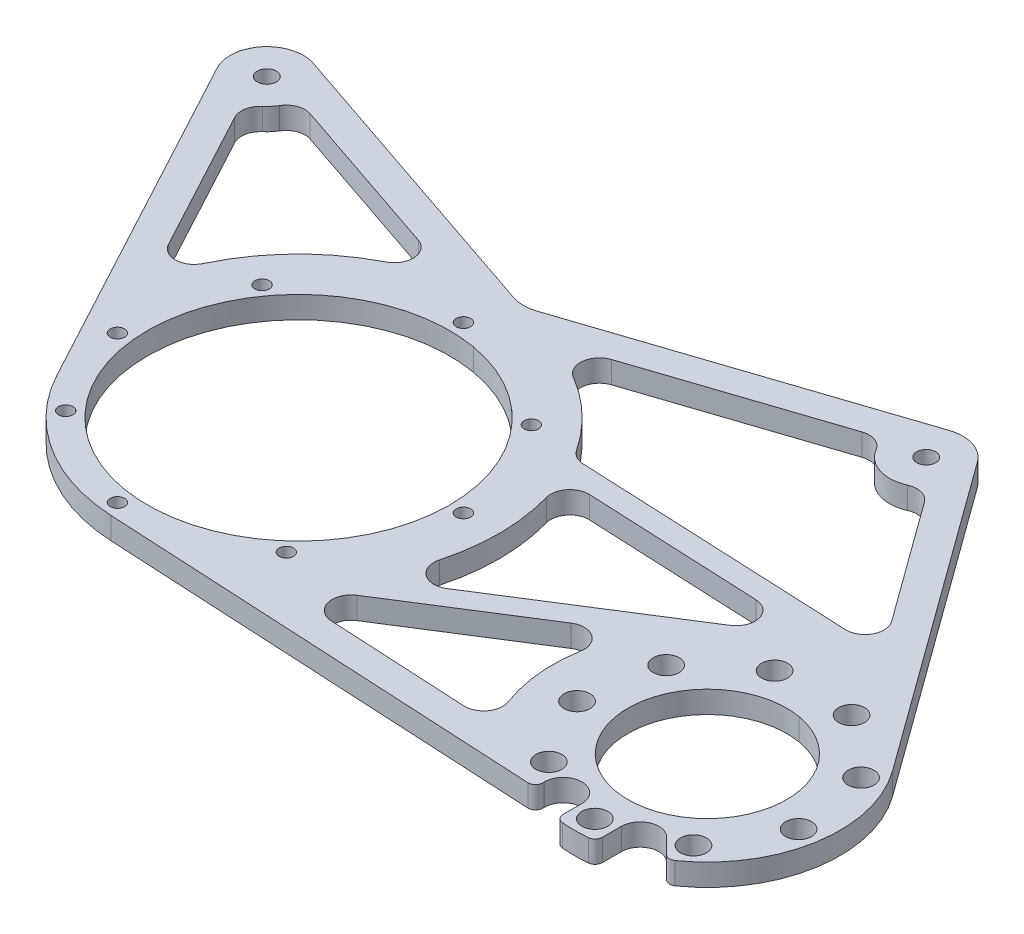
SolidWorks part; units mm, degrees
material "6061-T6 (SS)"
ref_plane "X-Y Datum" through (0, 0, 0) normal (0, 0, 1) x (1, 0, 0)
ref_plane "X-Z Datum" through (0, 0, 0) normal (0, 1, 0) x (1, 0, 0)
ref_plane "Y-Z Datum" through (0, 0, 0) normal (1, 0, 0) x (0, 0, -1)
sketch "Sketch2" plane through (0, 31.3819, 0) normal (0, 1, 0) x (1, 0, 0)
  line L0 (-693.7583, -176.702) -> (-693.7583, -183.2747) construction
  line L1 (-680.0808, -183.2747) -> (-680.0808, -176.702) construction
  line L2 (-668.9846, -172.1058) -> (-663.7197, -177.3707) construction
  line L3 (-693.7583, -176.702) -> (-693.7583, -183.2747)
  line L4 (-680.0808, -183.2747) -> (-680.0808, -176.702)
  line L5 (-668.9846, -172.1058) -> (-663.7197, -177.3707)
  line L6 (-966.641, -0.354) -> (-738.041, -0.354)
  line L7 (-727.7656, -5.5904) -> (-649.7224, -113.0358)
  line L9 (-977.8288, -19.0644) -> (-913.2312, -139.3061)
  line L10 (-706.7583, -177.279) -> (-706.7583, -176.702) construction
  line L11 (-706.7583, -177.279) -> (-706.7583, -176.702)
  line L12 (-861.9259, -171.8334) -> (-709.2983, -179.819)
  line L13 (-858.691, -110.0055) -> (-686.9195, -140.054) construction
  arc A0 (-710.607, -179.4559) -> (-706.7583, -177.279) centre (-709.2983, -177.279) ccw construction
  arc A1 (-693.7583, -176.702) -> (-706.7583, -176.702) centre (-700.2583, -176.702) ccw construction
  arc A2 (-693.7583, -183.2747) -> (-691.4697, -185.8023) centre (-691.2183, -183.2747) ccw construction
  arc A3 (-691.4697, -185.8023) -> (-682.3694, -185.8023) centre (-686.9195, -140.054) ccw construction
  arc A4 (-682.3694, -185.8023) -> (-680.0808, -183.2747) centre (-682.6208, -183.2747) ccw construction
  arc A5 (-668.9846, -172.1058) -> (-680.0808, -176.702) centre (-673.5808, -176.702) ccw construction
  arc A6 (-663.7197, -177.3707) -> (-660.4619, -177.6519) centre (-661.9236, -175.5746) ccw construction
  arc A7 (-660.4619, -177.6519) -> (-710.607, -179.4559) centre (-686.9195, -140.054) ccw construction
  circle A8 centre (-858.691, -110.0055) radius 52.3875 construction
  circle A9 centre (-858.691, -110.0055) radius 61.9125 construction
  circle A10 centre (-738.041, -13.054) radius 12.7 construction
  circle A11 centre (-966.641, -13.054) radius 12.7 construction
  arc A12 (-710.607, -179.4559) -> (-706.7583, -177.279) centre (-709.2983, -177.279) ccw
  arc A13 (-693.7583, -176.702) -> (-706.7583, -176.702) centre (-700.2583, -176.702) ccw
  arc A14 (-693.7583, -183.2747) -> (-691.4697, -185.8023) centre (-691.2183, -183.2747) ccw
  arc A15 (-691.4697, -185.8023) -> (-682.3694, -185.8023) centre (-686.9195, -140.054) ccw
  arc A16 (-682.3694, -185.8023) -> (-680.0808, -183.2747) centre (-682.6208, -183.2747) ccw
  arc A17 (-668.9846, -172.1058) -> (-680.0808, -176.702) centre (-673.5808, -176.702) ccw
  arc A18 (-663.7197, -177.3707) -> (-660.4619, -177.6519) centre (-661.9236, -175.5746) ccw
  arc A19 (-660.4619, -177.6519) -> (-710.607, -179.4559) centre (-686.9195, -140.054) ccw
  circle A20 centre (-858.691, -110.0055) radius 52.3875
  circle A21 centre (-858.691, -110.0055) radius 61.9125
  circle A22 centre (-738.041, -13.054) radius 12.7
  circle A23 centre (-966.641, -13.054) radius 12.7
  circle A24 centre (-901.1618, -148.2463) radius 2.5 construction
  circle A25 centre (-915.528, -115.9793) radius 2.5 construction
  circle A26 centre (-904.9264, -76.4135) radius 2.5 construction
  circle A27 centre (-858.691, -52.8555) radius 2.5 construction
  circle A28 centre (-816.2203, -71.7646) radius 2.5 construction
  circle A29 centre (-801.541, -110.0055) radius 2.5 construction
  circle A30 centre (-820.4502, -152.4762) radius 2.5 construction
  circle A31 centre (-864.6648, -166.8424) radius 2.5 construction
  circle A32 centre (-901.1618, -148.2463) radius 2.5
  circle A33 centre (-915.528, -115.9793) radius 2.5
  circle A34 centre (-904.9264, -76.4135) radius 2.5
  circle A35 centre (-858.691, -52.8555) radius 2.5
  circle A36 centre (-816.2203, -71.7646) radius 2.5
  circle A37 centre (-801.541, -110.0055) radius 2.5
  circle A38 centre (-820.4502, -152.4762) radius 2.5
  circle A39 centre (-864.6648, -166.8424) radius 2.5
  circle A40 centre (-686.9195, -140.054) radius 27.4955 construction
  circle A41 centre (-686.9195, -140.054) radius 27.4955
  circle A42 centre (-711.9883, -169.9297) radius 4.5 construction
  circle A43 centre (-725.3271, -146.8263) radius 4.5 construction
  circle A44 centre (-720.6945, -120.554) radius 4.5 construction
  circle A45 centre (-700.2583, -103.406) radius 4.5 construction
  circle A46 centre (-673.5808, -103.406) radius 4.5 construction
  circle A47 centre (-653.1446, -120.554) radius 4.5 construction
  circle A48 centre (-648.512, -146.8263) radius 4.5 construction
  circle A49 centre (-661.8508, -169.9297) radius 4.5 construction
  circle A50 centre (-686.9195, -179.054) radius 4.5 construction
  circle A51 centre (-711.9883, -169.9297) radius 4.5
  circle A52 centre (-725.3271, -146.8263) radius 4.5
  circle A53 centre (-720.6945, -120.554) radius 4.5
  circle A54 centre (-700.2583, -103.406) radius 4.5
  circle A55 centre (-673.5808, -103.406) radius 4.5
  circle A56 centre (-653.1446, -120.554) radius 4.5
  circle A57 centre (-648.512, -146.8263) radius 4.5
  circle A58 centre (-661.8508, -169.9297) radius 4.5
  circle A59 centre (-686.9195, -179.054) radius 4.5
  circle A60 centre (-966.641, -13.054) radius 3.3
  circle A61 centre (-738.041, -13.054) radius 3.3
  dimension "D1" = 6.6
  dimension "D2" = 6.6
extrude "Boss-Extrude1" add sketch "Sketch2" along normal blind 7.62 contours A21 A39 A38 A37 A36 A35 A34 A33 A32 A20 | A23 L9 A21 A19 L7 A22 L6 | A18 A19 A12 L11 A13 L3 A14 A15 A16 L4 A17 L5 A59 A58 A57 A56 A55 A54 A53 A52 A51 A41 | A23 A60 | A22 A61 | L13 A21 L12 A12 A19 region at (-700.2583, 31.3819, 168.9016) region at (-773.051, 31.3819, 154.3682) region at (-890.9045, 31.3819, 160.8157) region at (-815.2898, 31.3819, 52.4464) region at (-977.2328, 31.3819, 6.7207) region at (-726.304, 31.3819, 9.2412)
sketch "Sketch3" plane through (0, 31.3819, 0) normal (0, -1, 0) x (1, 0, 0)
  line L5 (-861.9259, 171.8334) -> (-709.2983, 179.819) construction
  line L6 (-977.8288, 19.0644) -> (-913.2312, 139.3061) construction
  line L7 (-727.7656, 5.5904) -> (-649.7224, 113.0358) construction
  line L16 (-966.641, 0.354) -> (-738.041, 0.354) construction
  line L19 (-663.7197, 177.3707) -> (-668.9846, 172.1058)
  line L20 (-680.0808, 176.702) -> (-680.0808, 183.2747)
  line L21 (-693.7583, 183.2747) -> (-693.7583, 176.702)
  line L22 (-706.7583, 176.702) -> (-706.7583, 177.279)
  line L23 (-663.7197, 177.3707) -> (-668.9846, 172.1058)
  line L24 (-680.0808, 176.702) -> (-680.0808, 183.2747)
  line L25 (-693.7583, 183.2747) -> (-693.7583, 176.702)
  line L26 (-706.7583, 176.702) -> (-706.7583, 177.279)
  line L28 (-861.9259, 171.8334) -> (-709.2983, 179.819)
  line L29 (-977.8288, 19.0644) -> (-913.2312, 139.3061)
  line L30 (-727.7656, 5.5904) -> (-649.7224, 113.0358)
  line L31 (-966.641, 0.354) -> (-738.041, 0.354)
  line L32 (-962.5646, 1.026) -> (-853.4371, 38.0109)
  line L33 (-853.4371, 38.0109) -> (-742.0453, 1.0018)
  circle A3 centre (-966.641, 13.054) radius 12.7
  circle A5 centre (-966.641, 13.054) radius 12.7
  circle A7 centre (-738.041, 13.054) radius 12.7
  circle A9 centre (-738.041, 13.054) radius 12.7
  circle A11 centre (-858.691, 110.0055) radius 61.9125
  circle A13 centre (-858.691, 110.0055) radius 61.9125
  circle A15 centre (-858.691, 110.0055) radius 52.3875
  circle A17 centre (-858.691, 110.0055) radius 52.3875
  circle A19 centre (-686.9195, 140.054) radius 27.4955
  circle A21 centre (-686.9195, 140.054) radius 27.4955
  circle A23 centre (-864.6648, 166.8424) radius 2.5
  circle A25 centre (-864.6648, 166.8424) radius 2.5
  circle A27 centre (-820.4502, 152.4762) radius 2.5
  circle A29 centre (-820.4502, 152.4762) radius 2.5
  circle A31 centre (-801.541, 110.0055) radius 2.5
  circle A33 centre (-801.541, 110.0055) radius 2.5
  circle A35 centre (-816.2203, 71.7646) radius 2.5
  circle A37 centre (-816.2203, 71.7646) radius 2.5
  circle A39 centre (-858.691, 52.8555) radius 2.5
  circle A41 centre (-858.691, 52.8555) radius 2.5
  circle A43 centre (-904.9264, 76.4135) radius 2.5
  circle A46 centre (-904.9264, 76.4135) radius 2.5
  circle A47 centre (-915.528, 115.9793) radius 2.5
  circle A48 centre (-915.528, 115.9793) radius 2.5
  circle A49 centre (-901.1618, 148.2463) radius 2.5
  circle A50 centre (-901.1618, 148.2463) radius 2.5
  circle A51 centre (-720.6945, 120.554) radius 4.5
  circle A52 centre (-720.6945, 120.554) radius 4.5
  circle A68 centre (-725.3271, 146.8263) radius 4.5
  circle A69 centre (-725.3271, 146.8263) radius 4.5
  circle A70 centre (-711.9883, 169.9297) radius 4.5
  circle A71 centre (-711.9883, 169.9297) radius 4.5
  circle A72 centre (-738.041, 13.054) radius 3.3
  circle A73 centre (-738.041, 13.054) radius 3.3
  circle A74 centre (-966.641, 13.054) radius 3.3
  circle A75 centre (-966.641, 13.054) radius 3.3
  circle A76 centre (-686.9195, 179.054) radius 4.5
  circle A77 centre (-686.9195, 179.054) radius 4.5
  circle A78 centre (-661.8508, 169.9297) radius 4.5
  circle A79 centre (-661.8508, 169.9297) radius 4.5
  circle A80 centre (-648.512, 146.8263) radius 4.5
  circle A81 centre (-648.512, 146.8263) radius 4.5
  circle A82 centre (-653.1446, 120.554) radius 4.5
  circle A83 centre (-653.1446, 120.554) radius 4.5
  circle A84 centre (-673.5808, 103.406) radius 4.5
  circle A85 centre (-673.5808, 103.406) radius 4.5
  circle A86 centre (-700.2583, 103.406) radius 4.5
  circle A87 centre (-700.2583, 103.406) radius 4.5
  arc A95 (-710.607, 179.4559) -> (-660.4619, 177.6519) centre (-686.9195, 140.054) ccw
  arc A96 (-660.4619, 177.6519) -> (-663.7197, 177.3707) centre (-661.9236, 175.5746) ccw
  arc A97 (-680.0808, 176.702) -> (-668.9846, 172.1058) centre (-673.5808, 176.702) ccw
  arc A98 (-680.0808, 183.2747) -> (-682.3694, 185.8023) centre (-682.6208, 183.2747) ccw
  arc A99 (-682.3694, 185.8023) -> (-691.4697, 185.8023) centre (-686.9195, 140.054) ccw
  arc A100 (-691.4697, 185.8023) -> (-693.7583, 183.2747) centre (-691.2183, 183.2747) ccw
  arc A101 (-706.7583, 176.702) -> (-693.7583, 176.702) centre (-700.2583, 176.702) ccw
  arc A102 (-706.7583, 177.279) -> (-710.607, 179.4559) centre (-709.2983, 177.279) ccw
  arc A103 (-710.607, 179.4559) -> (-660.4619, 177.6519) centre (-686.9195, 140.054) ccw
  arc A104 (-660.4619, 177.6519) -> (-663.7197, 177.3707) centre (-661.9236, 175.5746) ccw
  arc A105 (-680.0808, 176.702) -> (-668.9846, 172.1058) centre (-673.5808, 176.702) ccw
  arc A106 (-680.0808, 183.2747) -> (-682.3694, 185.8023) centre (-682.6208, 183.2747) ccw
  arc A107 (-682.3694, 185.8023) -> (-691.4697, 185.8023) centre (-686.9195, 140.054) ccw
  arc A108 (-691.4697, 185.8023) -> (-693.7583, 183.2747) centre (-691.2183, 183.2747) ccw
  arc A109 (-706.7583, 176.702) -> (-693.7583, 176.702) centre (-700.2583, 176.702) ccw
  arc A110 (-706.7583, 177.279) -> (-710.607, 179.4559) centre (-709.2983, 177.279) ccw
  line M47 (-966.641, 0.354) -> (-738.041, 0.354)
  dimension "D24" = 0
  dimension "D25" = 0
  dimension "D26" = 109.1275
  dimension "D27" = 36.9849
  dimension "D1" = 0
  dimension "D2" = 0
  dimension "D3" = 0
  dimension "D4" = 0
  dimension "D5" = 0
  dimension "D6" = 0
  dimension "D7" = 0
  dimension "D8" = 0
  dimension "D9" = 0
  dimension "D10" = 0
  dimension "D11" = 0
  dimension "D12" = 0
  dimension "D13" = 0
  dimension "D14" = 0
  dimension "D15" = 0
  dimension "D16" = 0
  dimension "D17" = 0
  dimension "D18" = 0
  dimension "D19" = 0
  dimension "D20" = 0
  dimension "D21" = 0
  dimension "D22" = 0
  dimension "D23" = 0
ref_point "Point1"
ref_point "Point2"
ref_plane "Plane1" through (-858.691, 31.3819, 110.0055) normal (0.985, 0, 0.1723) x (0.1723, 0, -0.985)
ref_plane "Plane2" through (-686.9195, 31.3819, 140.054) normal (-0.985, 0, -0.1723) x (-0.1723, 0, 0.985)
split line "Split Line1"
split line "Split Line2"
ref_axis "Axis1" through (-858.691, 39.0019, 110.0055) along (0, -1, 0)
ref_axis "Axis2" through (-686.9195, 39.0019, 140.054) along (0, -1, 0)
extrude "Cut-Extrude1" cut sketch "Sketch3" against normal through all contours A9 L33 L32 A5 M47 region at (-852.6937, 31.3819, 12.9049)
fillet "Fillet2" radius 12.7 1 edges at (-853.4371, 35.1919, 38.0109)
sketch "Sketch4" plane through (0, 31.3819, 0) normal (0, -1, 0) x (1, 0, 0)
  line L0 (-861.9259, 171.8334) -> (-709.2983, 179.819) construction
  line L1 (-727.7656, 5.5904) -> (-649.7224, 113.0358) construction
  line L2 (-977.8288, 19.0644) -> (-913.2312, 139.3061) construction
  line L3 (-962.5646, 1.026) -> (-853.4371, 38.0109) construction
  line L4 (-706.7583, 176.702) -> (-706.7583, 177.279)
  line L5 (-663.7197, 177.3707) -> (-668.9846, 172.1058)
  line L6 (-680.0808, 176.702) -> (-680.0808, 183.2747)
  line L7 (-693.7583, 183.2747) -> (-693.7583, 176.702)
  line L8 (-706.7583, 176.702) -> (-706.7583, 177.279)
  line L9 (-663.7197, 177.3707) -> (-668.9846, 172.1058)
  line L10 (-680.0808, 176.702) -> (-680.0808, 183.2747)
  line L11 (-693.7583, 183.2747) -> (-693.7583, 176.702)
  line L12 (-853.4371, 38.0109) -> (-742.0453, 1.0018) construction
  line L13 (-966.641, 0.354) -> (-738.041, 0.354) construction
  line L14 (-861.9259, 171.8334) -> (-709.2983, 179.819)
  line L15 (-727.7656, 5.5904) -> (-649.7224, 113.0358)
  line L16 (-977.8288, 19.0644) -> (-913.2312, 139.3061)
  line L17 (-962.5646, 1.026) -> (-853.4371, 38.0109)
  line L18 (-853.4371, 38.0109) -> (-742.0453, 1.0018)
  line L19 (-966.641, 0.354) -> (-738.041, 0.354)
  line L20 (-926.258, 93.5899) -> (-971.9278, 8.5803)
  line L21 (-971.9278, 8.5803) -> (-873.2671, 42.0179)
  line L22 (-732.3805, 168.4374) -> (-812.7818, 164.2308)
  line L23 (-812.7818, 164.2308) -> (-733.9678, 114.3873)
  line L24 (-799.833, 147.0258) -> (-703.8013, 86.2934)
  line L25 (-703.8013, 86.2934) -> (-794.9695, 82.1785)
  line L26 (-838.054, 43.606) -> (-750.6506, 14.5669)
  line L27 (-798.9847, 74.3695) -> (-686.6833, 79.4383)
  line L28 (-686.6833, 79.4383) -> (-728.6732, 21.6291)
  circle A1 centre (-858.691, 110.0055) radius 52.3875
  circle A2 centre (-858.691, 110.0055) radius 52.3875
  circle A3 centre (-858.691, 110.0055) radius 61.9125
  circle A4 centre (-858.691, 110.0055) radius 61.9125
  circle A5 centre (-738.041, 13.054) radius 12.7
  circle A6 centre (-738.041, 13.054) radius 12.7
  circle A7 centre (-966.641, 13.054) radius 12.7
  circle A8 centre (-966.641, 13.054) radius 12.7
  circle A9 centre (-858.691, 52.8555) radius 2.5
  circle A10 centre (-858.691, 52.8555) radius 2.5
  circle A11 centre (-816.2203, 71.7646) radius 2.5
  circle A12 centre (-816.2203, 71.7646) radius 2.5
  circle A13 centre (-801.541, 110.0055) radius 2.5
  circle A14 centre (-801.541, 110.0055) radius 2.5
  circle A15 centre (-820.4502, 152.4762) radius 2.5
  circle A16 centre (-820.4502, 152.4762) radius 2.5
  circle A17 centre (-864.6648, 166.8424) radius 2.5
  circle A18 centre (-864.6648, 166.8424) radius 2.5
  circle A19 centre (-686.9195, 140.054) radius 27.4955
  circle A20 centre (-686.9195, 140.054) radius 27.4955
  circle A21 centre (-725.3271, 146.8263) radius 4.5
  circle A22 centre (-725.3271, 146.8263) radius 4.5
  circle A23 centre (-720.6945, 120.554) radius 4.5
  circle A24 centre (-720.6945, 120.554) radius 4.5
  circle A25 centre (-901.1618, 148.2463) radius 2.5
  circle A26 centre (-901.1618, 148.2463) radius 2.5
  circle A27 centre (-915.528, 115.9793) radius 2.5
  circle A28 centre (-915.528, 115.9793) radius 2.5
  circle A29 centre (-904.9264, 76.4135) radius 2.5
  circle A30 centre (-904.9264, 76.4135) radius 2.5
  circle A31 centre (-661.8508, 169.9297) radius 4.5
  circle A32 centre (-661.8508, 169.9297) radius 4.5
  circle A33 centre (-686.9195, 179.054) radius 4.5
  circle A34 centre (-686.9195, 179.054) radius 4.5
  circle A35 centre (-966.641, 13.054) radius 3.3
  circle A36 centre (-966.641, 13.054) radius 3.3
  circle A37 centre (-738.041, 13.054) radius 3.3
  circle A38 centre (-738.041, 13.054) radius 3.3
  circle A39 centre (-711.9883, 169.9297) radius 4.5
  circle A40 centre (-711.9883, 169.9297) radius 4.5
  circle A41 centre (-700.2583, 103.406) radius 4.5
  circle A42 centre (-700.2583, 103.406) radius 4.5
  circle A43 centre (-673.5808, 103.406) radius 4.5
  circle A44 centre (-673.5808, 103.406) radius 4.5
  circle A45 centre (-653.1446, 120.554) radius 4.5
  circle A46 centre (-653.1446, 120.554) radius 4.5
  circle A47 centre (-648.512, 146.8263) radius 4.5
  circle A48 centre (-648.512, 146.8263) radius 4.5
  arc A49 (-873.2671, 42.0179) -> (-926.258, 93.5899) centre (-858.691, 110.0055) cw
  arc A50 (-732.3805, 168.4374) -> (-733.9678, 114.3873) centre (-686.9195, 140.054) ccw
  arc A51 (-799.833, 147.0258) -> (-794.9695, 82.1785) centre (-858.691, 110.0055) cw
  arc A52 (-838.054, 43.606) -> (-798.9847, 74.3695) centre (-858.691, 110.0055) ccw
  arc A56 (-706.7583, 177.279) -> (-710.607, 179.4559) centre (-709.2983, 177.279) ccw
  arc A57 (-710.607, 179.4559) -> (-660.4619, 177.6519) centre (-686.9195, 140.054) ccw
  arc A58 (-660.4619, 177.6519) -> (-663.7197, 177.3707) centre (-661.9236, 175.5746) ccw
  arc A59 (-680.0808, 176.702) -> (-668.9846, 172.1058) centre (-673.5808, 176.702) ccw
  arc A60 (-680.0808, 183.2747) -> (-682.3694, 185.8023) centre (-682.6208, 183.2747) ccw
  arc A61 (-682.3694, 185.8023) -> (-691.4697, 185.8023) centre (-686.9195, 140.054) ccw
  arc A62 (-691.4697, 185.8023) -> (-693.7583, 183.2747) centre (-691.2183, 183.2747) ccw
  arc A63 (-706.7583, 176.702) -> (-693.7583, 176.702) centre (-700.2583, 176.702) ccw
  arc A64 (-706.7583, 177.279) -> (-710.607, 179.4559) centre (-709.2983, 177.279) ccw
  arc A65 (-710.607, 179.4559) -> (-660.4619, 177.6519) centre (-686.9195, 140.054) ccw
  arc A66 (-660.4619, 177.6519) -> (-663.7197, 177.3707) centre (-661.9236, 175.5746) ccw
  arc A67 (-680.0808, 176.702) -> (-668.9846, 172.1058) centre (-673.5808, 176.702) ccw
  arc A68 (-680.0808, 183.2747) -> (-682.3694, 185.8023) centre (-682.6208, 183.2747) ccw
  arc A69 (-682.3694, 185.8023) -> (-691.4697, 185.8023) centre (-686.9195, 140.054) ccw
  arc A70 (-691.4697, 185.8023) -> (-693.7583, 183.2747) centre (-691.2183, 183.2747) ccw
  arc A71 (-706.7583, 176.702) -> (-693.7583, 176.702) centre (-700.2583, 176.702) ccw
  dimension "D26" = 7.62
  dimension "D29" = 7.62
  dimension "D30" = 7.62
  dimension "D35" = 10.16
  dimension "D39" = 7.62
  dimension "D27" = 10.16
  dimension "D28" = 10.16
  dimension "D31" = 10.16
  dimension "D32" = 7.62
  dimension "D33" = 93.2524
  dimension "D34" = 49.8435
  dimension "D36" = 91.1683
  dimension "D37" = 4.1149
  dimension "D38" = 10.16
  dimension "D40" = 7.62
  dimension "D1" = 0
  dimension "D2" = 0
  dimension "D3" = 0
  dimension "D4" = 0
  dimension "D5" = 0
  dimension "D6" = 0
  dimension "D7" = 0
  dimension "D8" = 0
  dimension "D9" = 0
  dimension "D10" = 0
  dimension "D11" = 0
  dimension "D12" = 0
  dimension "D13" = 0
  dimension "D14" = 0
  dimension "D15" = 0
  dimension "D16" = 0
  dimension "D17" = 0
  dimension "D18" = 0
  dimension "D19" = 0
  dimension "D20" = 0
  dimension "D21" = 0
  dimension "D22" = 0
  dimension "D23" = 0
  dimension "D24" = 0
  dimension "D25" = 0
extrude "Cut-Extrude2" cut sketch "Sketch4" against normal through all contours L21 A49 L20 A8 | A52 L26 A6 L28 L27 | L24 A51 L25 | A50 L22 L23 region at (-925.9258, 31.3819, 46.4397) region at (-758.7542, 31.3819, 51.2527) region at (-763.0306, 31.3819, 150.0769) region at (-762.4094, 31.3819, 103.8535)
fillet "Fillet3" radius 6.604 15 edges at (-733.9678, 35.1919, 114.3873) (-732.3805, 35.1919, 168.4374) (-812.7818, 35.1919, 164.2308) (-703.8013, 35.1919, 86.2934) (-794.9695, 35.1919, 82.1785) (-799.833, 35.1919, 147.0258) (-686.6833, 35.1919, 79.4383) (-798.9847, 35.1919, 74.3695) (-838.054, 35.1919, 43.606) (-750.6506, 35.1919, 14.5669) (-728.6732, 35.1919, 21.6291) (-954.0408, 35.1919, 14.6425) (-962.9896, 35.1919, 25.2177) (-873.2671, 35.1919, 42.0179) (-926.258, 35.1919, 93.5899)
split line "Split Line3"
sketch "Sketch2<4>" plane through (0, 31.3819, 0) normal (0, 1, 0) x (1, 0, 0) same geometry as "Sketch2"
